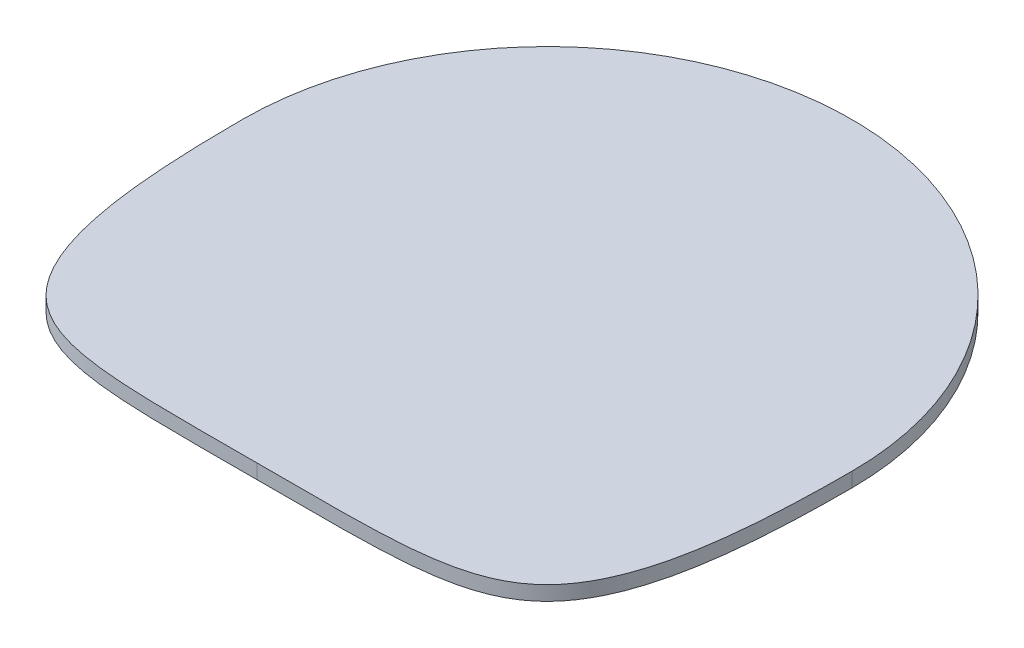
SolidWorks part; units mm, degrees
ref_plane "Front Plane" through (0, 0, 0) normal (0, 0, 1) x (1, 0, 0)
ref_plane "Top Plane" through (0, 0, 0) normal (0, 1, 0) x (1, 0, 0)
ref_plane "Right Plane" through (0, 0, 0) normal (1, 0, 0) x (0, 0, -1)
sketch "Sketch1" plane through (0, 0, 0) normal (0, 1, 0) x (1, 0, 0)
  line L0 (0, 0) -> (-157.9039, -157.9039) construction
  line L1 (0, -127) -> (0, 133.35) construction
  arc A0 (133.35, 0) -> (-133.35, 0) centre (0, 0) ccw
  spline S0 degree 3 poles (-133.35, 0) (-133.35, -51.198) (-123.8034, -129.8051) (-58.428, -127) (0, -127) knots 0 0 0 0 0.502616 1 1 1 1
  spline S1 degree 3 poles (133.35, 0) (133.35, -51.198) (123.8034, -129.8051) (58.428, -127) (0, -127) knots 0 0 0 0 0.502616 1 1 1 1
  dimension "D1" = 266.7
extrude "Base" add sketch "Sketch1" along normal blind 6.35
sketch "ShaftLayout" plane through (0, 6.35, 0) normal (0, 1, 0) x (1, 0, 0)
  line L0 (-133.35, 0) -> (133.35, 0) construction
  line L1 (0, 133.35) -> (0, -127) construction
  line L2 (-115.4124, -6.35) -> (-105.5064, -6.35)
  line L3 (-38.3624, -38) -> (-96.3624, -38)
  line L4 (-38.3624, -38) -> (-38.3624, 38)
  line L5 (-38.3624, 38) -> (-96.3624, 38)
  line L6 (-96.3624, -38) -> (-96.3624, 38)
  line L7 (-38.3624, -38) -> (-96.3624, 38) construction
  line L8 (-38.3624, 38) -> (-96.3624, -38) construction
  line L9 (-102.7124, -15.875) -> (-105.5064, -15.875)
  line L10 (-102.7124, -15.875) -> (-102.7124, 15.875)
  line L11 (-102.7124, 15.875) -> (-105.5064, 15.875)
  line L12 (-105.5064, -15.875) -> (-105.5064, 15.875)
  line L13 (-102.7124, -15.875) -> (-105.5064, 15.875) construction
  line L14 (-102.7124, 15.875) -> (-105.5064, -15.875) construction
  line L15 (-115.4124, -6.35) -> (-115.4124, 6.35)
  line L16 (-105.5064, -6.35) -> (-105.5064, 6.35)
  line L17 (-115.4124, 6.35) -> (-105.5064, 6.35)
  line L18 (-115.4124, -6.35) -> (-105.5064, 6.35) construction
  line L19 (-105.5064, -6.35) -> (-115.4124, 6.35) construction
  line L20 (-116.9999, -9.525) -> (-115.4124, -9.525)
  line L21 (-116.9999, -9.525) -> (-116.9999, 9.525)
  line L22 (-115.4124, -9.525) -> (-115.4124, 9.525)
  line L23 (-116.9999, 9.525) -> (-115.4124, 9.525)
  line L24 (-116.9999, -9.525) -> (-115.4124, 9.525) construction
  line L25 (-115.4124, -9.525) -> (-116.9999, 9.525) construction
  line L26 (-128.1124, -7.9375) -> (-116.9999, -7.9375)
  line L27 (-128.1124, -7.9375) -> (-128.1124, 7.9375)
  line L28 (-116.9999, -7.9375) -> (-116.9999, 7.9375)
  line L29 (-128.1124, 7.9375) -> (-116.9999, 7.9375)
  line L30 (-128.1124, -7.9375) -> (-116.9999, 7.9375) construction
  line L31 (-116.9999, -7.9375) -> (-128.1124, 7.9375) construction
  line L32 (-19.3124, -7.9375) -> (-30.4249, -7.9375)
  line L33 (-32.0124, -9.525) -> (-30.4249, -9.525)
  line L34 (-32.0124, -9.525) -> (-32.0124, 9.525)
  line L35 (-32.0124, 9.525) -> (-30.4249, 9.525)
  line L36 (-30.4249, -9.525) -> (-30.4249, 9.525)
  line L37 (-32.0124, -9.525) -> (-30.4249, 9.525) construction
  line L38 (-32.0124, 9.525) -> (-30.4249, -9.525) construction
  line L39 (-19.3124, -7.9375) -> (-19.3124, 7.9375)
  line L40 (-30.4249, -7.9375) -> (-30.4249, 7.9375)
  line L41 (-19.3124, 7.9375) -> (-30.4249, 7.9375)
  line L42 (-19.3124, -7.9375) -> (-30.4249, 7.9375) construction
  line L43 (-30.4249, -7.9375) -> (-19.3124, 7.9375) construction
  arc A0 (133.35, 0) -> (-133.35, 0) centre (0, 0) ccw construction
  point P10 (-67.3624, 0)
  point P15 (-104.1094, 0)
  point P20 (-31.2186, 0)
  point P21 (-110.4594, 0)
  point P22 (-116.2061, 0)
  point P23 (-122.5561, 0)
  point P41 (-24.8686, 0)
  dimension "D1" = 58
  dimension "D2" = 76
  dimension "D3" = 6.35
  dimension "D4" = 2.794
  dimension "D5" = 31.75
  dimension "D6" = 9.906
  dimension "D7" = 12.7
  dimension "D8" = 19.05
  dimension "D9" = 1.5875
  dimension "D10" = 12.7
  dimension "D11" = 15.875
  dimension "D12" = 19.05
  dimension "D13" = 1.5875
  dimension "D14" = 15.875
  dimension "D15" = 12.7
  dimension "D16" = 6.35
sketch "MotorLayout" plane through (0, 6.35, 0) normal (0, 1, 0) x (1, 0, 0)
  line L0 (-99.7124, -85.55) -> (-119.7124, -85.55) construction
  line L1 (-99.7124, -114.05) -> (-23.7124, -114.05)
  line L2 (-99.7124, -114.05) -> (-99.7124, -57.05)
  line L3 (-99.7124, -57.05) -> (-23.7124, -57.05)
  line L4 (-23.7124, -114.05) -> (-23.7124, -57.05)
  line L5 (-99.7124, -114.05) -> (-23.7124, -57.05) construction
  line L6 (-99.7124, -57.05) -> (-23.7124, -114.05) construction
  line L7 (-115.4124, -95.8687) -> (-105.5064, -95.8687)
  line L8 (-105.5064, -101.425) -> (-102.7124, -101.425)
  line L9 (-105.5064, -101.425) -> (-105.5064, -69.675)
  line L10 (-105.5064, -69.675) -> (-102.7124, -69.675)
  line L11 (-102.7124, -101.425) -> (-102.7124, -69.675)
  line L12 (-105.5064, -101.425) -> (-102.7124, -69.675) construction
  line L13 (-105.5064, -69.675) -> (-102.7124, -101.425) construction
  line L14 (-38.3624, -38) -> (-96.3624, -38) construction
  line L15 (-115.4124, -95.8687) -> (-115.4124, -75.2312)
  line L16 (-105.5064, -95.8687) -> (-105.5064, -75.2312)
  line L17 (-115.4124, -75.2312) -> (-105.5064, -75.2312)
  line L18 (-115.4124, -95.8687) -> (-105.5064, -75.2312) construction
  line L19 (-105.5064, -95.8687) -> (-115.4124, -75.2312) construction
  line L20 (-104.1094, -1000) -> (-104.1094, 49000) construction
  point P0 (-61.7124, -85.55)
  point P7 (-104.1094, -85.55)
  point P14 (-110.4594, -85.55)
  dimension "D1" = 20
  dimension "D2" = 76
  dimension "D3" = 57
  dimension "D4" = 2.794
  dimension "D5" = 19.05
  dimension "D6" = 31.75
  dimension "D7" = 20.6375
  dimension "D8" = 12.7
  dimension "D9" = 3
